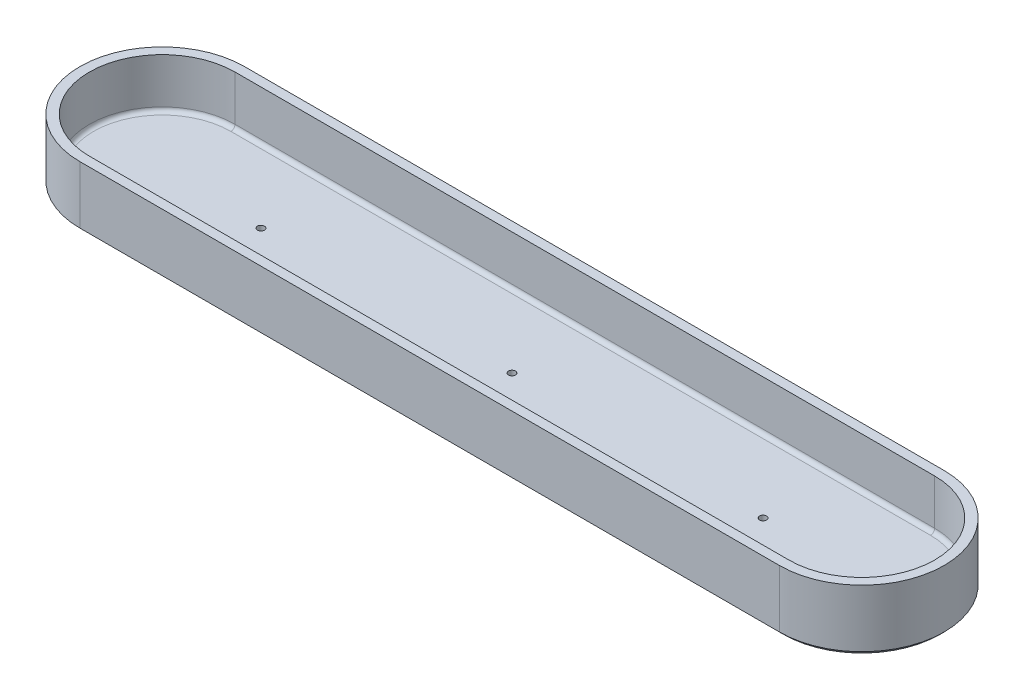
SolidWorks part; units mm, degrees
ref_plane "Front Plane" through (0, 0, 0) normal (0, 0, 1) x (1, 0, 0)
ref_plane "Top Plane" through (0, 0, 0) normal (0, 1, 0) x (1, 0, 0)
ref_plane "Right Plane" through (0, 0, 0) normal (1, 0, 0) x (0, 0, -1)
sketch "Sketch1" plane through (0, 0, 0) normal (0, 1, 0) x (1, 0, 0)
  line L0 (-107.95, 0) -> (107.95, 0) construction
  line L1 (0, -55.9739) -> (0, 55.9739) construction
  line L2 (-107.95, 22.479) -> (107.95, 22.479)
  line L3 (-107.95, -22.479) -> (107.95, -22.479)
  arc A0 (-107.95, 22.479) -> (-107.95, -22.479) centre (-107.95, 0) ccw
  arc A1 (107.95, 22.479) -> (107.95, -22.479) centre (107.95, 0) cw
  point P4 (0, 0)
  point P10 (0, 0)
  dimension "D2" = 44.958
  dimension "D1" = 215.9
extrude "MainBlock" add sketch "Sketch1" along normal blind 3.81
sketch "Sketch2" plane through (0, 0, 0) normal (0, -1, 0) x (1, 0, 0)
  line L0 (0, 0) -> (0, 50000) construction
  line L1 (-107.95, 25.4) -> (107.95, 25.4)
  line L2 (-107.95, -22.479) -> (107.95, -22.479)
  line L3 (107.95, 22.479) -> (-107.95, 22.479)
  line L5 (107.95, 22.479) -> (-107.95, 22.479)
  line L6 (-95.25, 0) -> (49904.75, 0) construction
  line L7 (107.95, -22.479) -> (-107.95, -22.479)
  line L8 (-107.95, -25.4) -> (107.95, -25.4)
  arc A0 (-107.95, 25.4) -> (-107.95, -25.4) centre (-107.95, 0) ccw
  arc A1 (107.95, 22.479) -> (107.95, -22.479) centre (107.95, 0) cw
  arc A2 (-107.95, 22.479) -> (-107.95, -22.479) centre (-107.95, 0) ccw
  arc A3 (107.95, -22.479) -> (107.95, 22.479) centre (107.95, 0) ccw
  arc A4 (-107.95, 22.479) -> (-107.95, -22.479) centre (-107.95, 0) ccw
  arc A6 (107.95, 25.4) -> (107.95, -25.4) centre (107.95, 0) cw
  point P0 (0, 22.479)
  point P15 (0, 25.4)
  point P16 (0, -22.479)
  point P19 (0, -25.4)
  dimension "2.1" = 50.8
  dimension "D1" = 0
extrude "Boss-Extrude1" add sketch "Sketch2" against normal blind 19.05
sketch "Sketch3" plane through (0, 0, 0) normal (0, -1, 0) x (1, 0, 0)
  line L0 (0, 0) -> (50000, 0) construction
  line L1 (0, 0) -> (0, 50000) construction
  circle A1 centre (0, 0) radius 1.0795
  circle A8 centre (-77.47, 0) radius 1.0795
  circle A9 centre (77.47, 0) radius 1.0795
  arc A10 (107.95, -25.4) -> (107.95, 25.4) centre (107.95, 0) ccw construction
  arc A11 (-107.95, 25.4) -> (-107.95, -25.4) centre (-107.95, 0) ccw construction
  arc A12 (107.95, -25.4) -> (107.95, 25.4) centre (107.95, 0) ccw construction
  arc A13 (-107.95, 25.4) -> (-107.95, -25.4) centre (-107.95, 0) ccw construction
  dimension "0.085" = 2.159
  dimension "D2" = 2.159
  dimension "D3" = 2.159
  dimension "D4" = 30.48
  dimension "D5" = 30.48
extrude "Cut-Extrude1" cut sketch "Sketch3" against normal through all
fillet "Fillet1" radius 1.27 4 edges at (130.429, 3.81, 0) (0, 3.81, 22.479) (-130.429, 3.81, 0) (0, 3.81, -22.479)
chamfer "Chamfer1" distance 1.27 angle 45 4 edges at (0, 0, 25.4) (-133.35, 0, 0) (133.35, 0, 0) (0, 0, -25.4)
equation "\"D2@Sketch3\"=\"0.085@Sketch3\""
equation "\"D3@Sketch3\"=\"0.085@Sketch3\""
